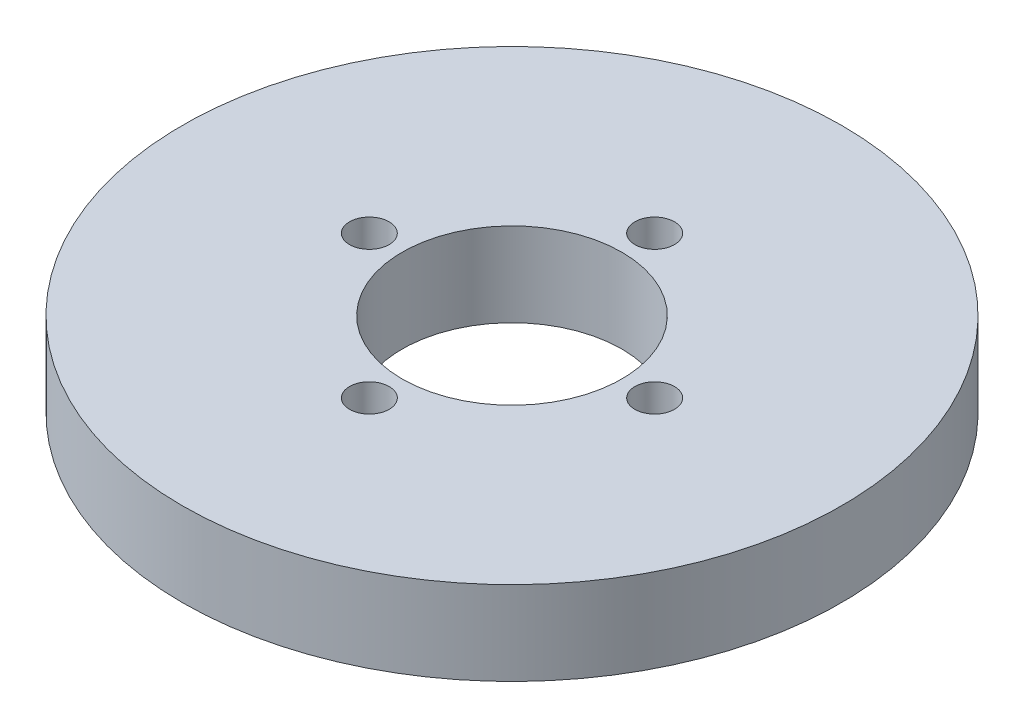
SolidWorks part; units mm, degrees
ref_plane "Front Plane" through (0, 0, 0) normal (0, 0, 1) x (1, 0, 0)
ref_plane "Top Plane" through (0, 0, 0) normal (0, 1, 0) x (1, 0, 0)
ref_plane "Right Plane" through (0, 0, 0) normal (1, 0, 0) x (0, 0, -1)
sketch "Sketch1" plane through (0, 0, 0) normal (0, 1, 0) x (1, 0, 0)
  circle A0 centre (0, 0) radius 82.5
  dimension "FLANGE_OD" = 165
extrude "Boss-Extrude1" add sketch "Sketch1" along normal blind 21
sketch "Sketch2" plane through (0, 0, 0) normal (0, 1, 0) x (1, 0, 0)
  circle A0 centre (0, 0) radius 27.5
  dimension "BORE_D" = 55
extrude "Cut-Extrude1" cut sketch "Sketch2" along normal through all
sketch "Sketch3" plane through (0, 21, 0) normal (0, 1, 0) x (1, 0, 0)
  circle A0 centre (0, 0) radius 35.7151 construction
  circle A1 centre (-35.7151, 0) radius 4.9579
  dimension "BOLT_D" = 9.9158
  dimension "BOLT_PCD" = 71.4302
extrude "Cut-Extrude2" cut sketch "Sketch3" against normal blind 14.7858
pattern_circular "CirPattern1" count 4 over 360 about axis through (0, 0, 0) along (0, 1, 0) of "Cut-Extrude2"
